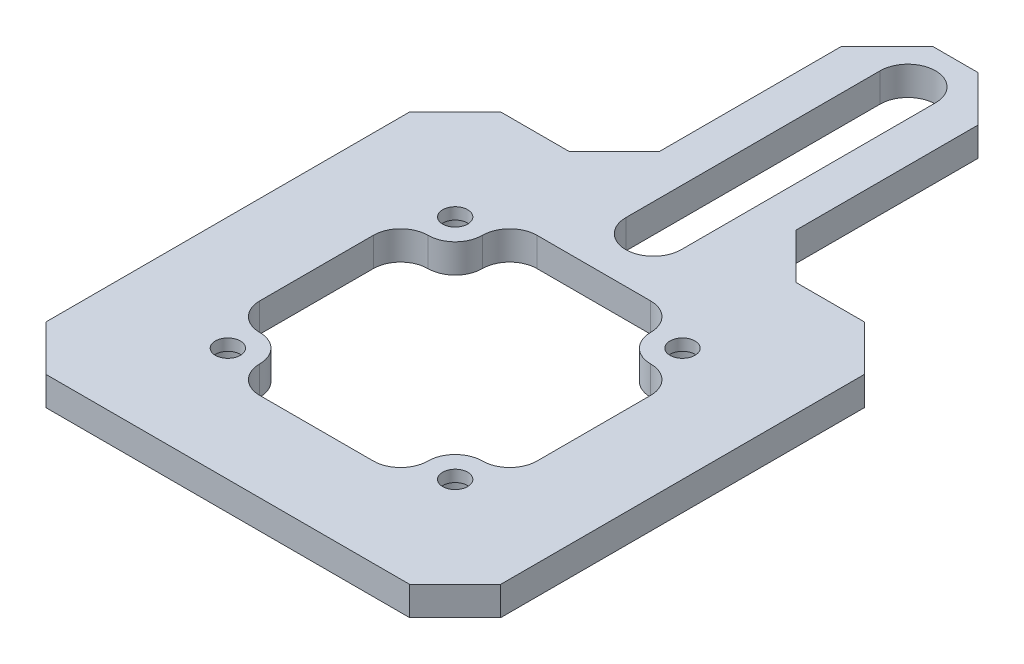
SolidWorks part; units mm, degrees
ref_plane "Front Plane" through (0, 0, 0) normal (0, 0, 1) x (1, 0, 0)
ref_plane "Top Plane" through (0, 0, 0) normal (0, 1, 0) x (1, 0, 0)
ref_plane "Right Plane" through (0, 0, 0) normal (1, 0, 0) x (0, 0, -1)
sketch "Sketch2" plane through (0, 0, 0) normal (0, 1, 0) x (1, 0, 0)
  line L1 (-25, -25) -> (25, -25)
  line L2 (-25, -25) -> (-25, 25)
  line L3 (-25, 25) -> (25, 25)
  line L4 (25, -25) -> (25, 25)
  line L5 (-25, -25) -> (25, 25) construction
  line L6 (-25, 25) -> (25, -25) construction
  point P0 (0, 0)
  dimension "D1" = 50
  dimension "D2" = 50
extrude "Boss-Extrude1" add sketch "Sketch2" along normal blind 3.175
sketch "Sketch3" plane through (0, 3.175, 0) normal (0, 1, 0) x (1, 0, 0)
  line L1 (-12.5, 12.5) -> (12.5, 12.5) construction
  line L2 (-12.5, 12.5) -> (-12.5, -12.5) construction
  line L3 (-12.5, -12.5) -> (12.5, -12.5) construction
  line L4 (12.5, 12.5) -> (12.5, -12.5) construction
  line L5 (-12.5, 12.5) -> (12.5, -12.5) construction
  line L6 (-12.5, -12.5) -> (12.5, 12.5) construction
  circle A0 centre (12.25, -12.25) radius 1.0508 construction
  circle A1 centre (-12.25, -12.25) radius 1.05 construction
  circle A2 centre (12.25, 12.25) radius 1.0508 construction
  circle A3 centre (-12.25, 12.25) radius 1.05 construction
  circle A4 centre (12.25, -12.25) radius 1.0508 construction
  circle A5 centre (-12.25, -12.25) radius 1.05 construction
  circle A6 centre (12.25, 12.25) radius 1.0508 construction
  circle A7 centre (-12.25, 12.25) radius 1.05 construction
  circle A8 centre (12.5, 12.5) radius 1.375
  circle A9 centre (-12.5, 12.5) radius 1.375
  circle A10 centre (-12.5, -12.5) radius 1.375
  circle A11 centre (12.5, -12.5) radius 1.375
  point P12 (0, 0)
  dimension "D3" = 2.75
  dimension "D1" = 25
  dimension "D2" = 25
  dimension "D4" = 2
  dimension "D5" = 2
extrude "Cut-Extrude1" cut sketch "Sketch3" against normal through all
sketch "Sketch5" plane through (0, 0, 0) normal (0, -1, 0) x (1, 0, 0)
  circle A4 centre (12.5, 12.5) radius 2.375
  circle A5 centre (-12.5, 12.5) radius 2.375
  circle A6 centre (-12.5, 12.5) radius 2.375
  circle A7 centre (12.5, -12.5) radius 2.375
  circle A8 centre (-12.5, -12.5) radius 2.375
  dimension "D4" = 1
  dimension "D5" = 2
  dimension "D6" = 2
extrude "Cut-Extrude3" cut sketch "Sketch5" against normal blind 1.9
sketch "Sketch10" plane through (0, 0, 0) normal (0, -1, 0) x (1, 0, 0)
  line L1 (15.25, -15.25) -> (-15.25, -15.25)
  line L2 (15.25, -15.25) -> (15.25, 15.25)
  line L3 (15.25, 15.25) -> (-15.25, 15.25)
  line L4 (-15.25, -15.25) -> (-15.25, 15.25)
  line L5 (15.25, -15.25) -> (-15.25, 15.25) construction
  line L6 (15.25, 15.25) -> (-15.25, -15.25) construction
  line L7 (-15.25, -15.25) -> (-9.25, -15.25)
  line L8 (-15.25, -15.25) -> (-15.25, -9.25)
  line L9 (-15.25, -9.25) -> (-9.25, -9.25)
  line L10 (-9.25, -15.25) -> (-9.25, -9.25)
  line L11 (-15.25, 15.25) -> (-9.25, 15.25)
  line L12 (-15.25, 15.25) -> (-15.25, 9.25)
  line L13 (-15.25, 9.25) -> (-9.25, 9.25)
  line L14 (-9.25, 15.25) -> (-9.25, 9.25)
  line L15 (15.25, 15.25) -> (9.25, 15.25)
  line L16 (15.25, 15.25) -> (15.25, 9.25)
  line L17 (15.25, 9.25) -> (9.25, 9.25)
  line L18 (9.25, 15.25) -> (9.25, 9.25)
  line L19 (15.25, -15.25) -> (9.25, -15.25)
  line L20 (15.25, -15.25) -> (15.25, -9.25)
  line L21 (15.25, -9.25) -> (9.25, -9.25)
  line L22 (9.25, -15.25) -> (9.25, -9.25)
  point P0 (0, 0)
  dimension "D1" = 30.5
  dimension "D2" = 30.5
  dimension "D3" = 6
extrude "Cut-Extrude9" cut sketch "Sketch10" against normal through all contours L1 L22 L21 L2 L17 L18 L3 L14 L13 L4 L9 L10 region at (0, 0, 0)
fillet "Fillet1" radius 3 12 edges at (15.25, 1.5875, -9.25) (15.25, 1.5875, 9.25) (-9.25, 1.5875, -15.25) (9.25, 1.5875, -15.25) (9.25, 1.5875, 15.25) (-9.25, 1.5875, 15.25) (-15.25, 1.5875, 9.25) (-15.25, 1.5875, -9.25) (9.25, 1.5875, 9.25) (-9.25, 1.5875, 9.25) (9.25, 1.5875, -9.25) (-9.25, 1.5875, -9.25)
sketch "Sketch11" plane through (0, 3.175, 0) normal (0, 1, 0) x (1, 0, 0)
  line L0 (0, 25) -> (0, 74.5657) construction
  line L1 (25, 25) -> (-25, 25) construction
  line L2 (0, 49.7829) -> (0, 21.8135) construction
  line L3 (-7.5, 55) -> (7.5, 55)
  line L4 (-7.5, 55) -> (-7.5, 25)
  line L5 (-7.5, 25) -> (7.5, 25)
  line L6 (7.5, 55) -> (7.5, 25)
  line L7 (-7.5, 55) -> (7.5, 25) construction
  line L8 (-7.5, 25) -> (7.5, 55) construction
  line L9 (3.05, 49.7829) -> (3.05, 21.8135)
  line L10 (-3.05, 49.7829) -> (-3.05, 21.8135)
  arc A0 (3.05, 49.7829) -> (-3.05, 49.7829) centre (0, 49.7829) ccw
  arc A1 (-3.05, 21.8135) -> (3.05, 21.8135) centre (0, 21.8135) ccw
  point P5 (0, 40)
  point P12 (0, 35.7982)
  line M12 (25, 25) -> (-25, 25)
  dimension "D3" = 3.05
  dimension "D1" = 30
  dimension "D2" = 15
extrude "Boss-Extrude2" add sketch "Sketch11" against normal up to surface (3.175 mm away) contours A0 L9 L6 L3 L4 L10 M12 | L10 A0 L9 A1 region at (0, 3.175, -54.6646) up to face at (-12.5, 0, -14.875)
sketch "Sketch13" plane through (0, 3.175, 0) normal (0, 1, 0) x (1, 0, 0)
  line L0 (-3.05, 49.7829) -> (-3.05, 21.8135) construction
  line L1 (3.05, 49.7829) -> (3.05, 21.8135) construction
  line L2 (-3.05, 49.7829) -> (-3.05, 21.8135)
  line L3 (3.05, 49.7829) -> (3.05, 21.8135)
  arc A1 (3.05, 49.7829) -> (-3.05, 49.7829) centre (0, 49.7829) ccw construction
  arc A2 (-3.05, 21.8135) -> (3.05, 21.8135) centre (0, 21.8135) ccw construction
  arc A3 (3.05, 49.7829) -> (-3.05, 49.7829) centre (0, 49.7829) ccw
  arc A4 (-3.05, 21.8135) -> (3.05, 21.8135) centre (0, 21.8135) ccw
extrude "Cut-Extrude10" cut sketch "Sketch13" against normal up to next
chamfer "Chamfer1" distance 5 angle 45 8 edges at (25, 1.5875, -25) (25, 1.5875, 25) (-25, 1.5875, 25) (-25, 1.5875, -25) (-7.5, 1.5875, -25) (7.5, 1.5875, -25) (7.5, 1.5875, -55) (-7.5, 1.5875, -55)
ref_point "Point1"
